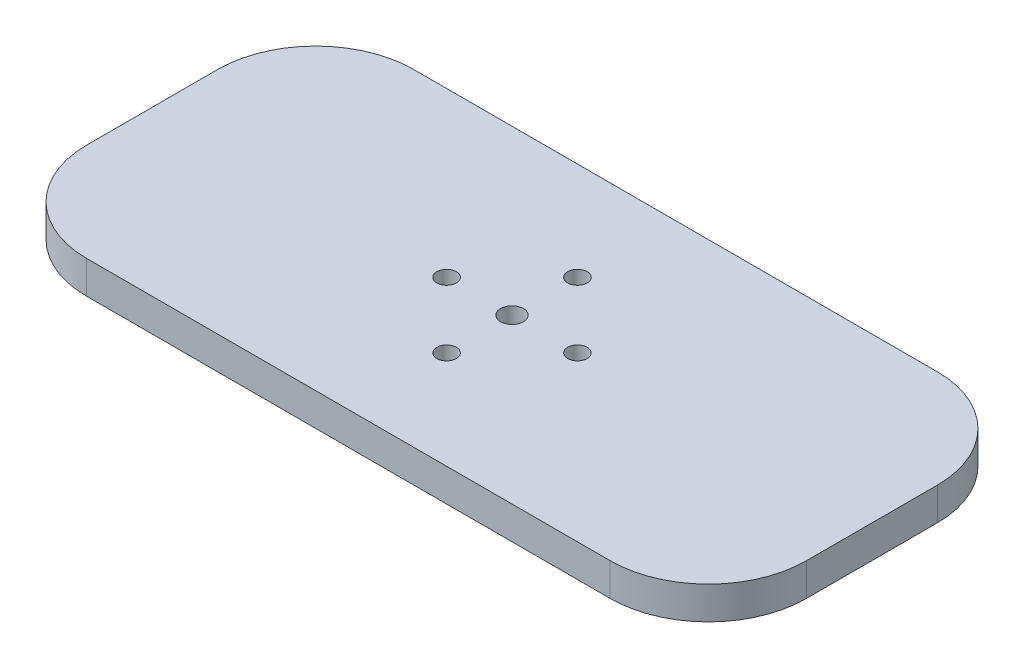
SolidWorks part; units mm, degrees
ref_plane "Front Plane" through (0, 0, 0) normal (0, 0, 1) x (1, 0, 0)
ref_plane "Top Plane" through (0, 0, 0) normal (0, 1, 0) x (1, 0, 0)
ref_plane "Right Plane" through (0, 0, 0) normal (1, 0, 0) x (0, 0, -1)
sketch "Sketch1" plane through (0, 0, 0) normal (0, 1, 0) x (1, 0, 0)
  line L1 (-69.85, -31.75) -> (69.85, -31.75)
  line L2 (-69.85, -31.75) -> (-69.85, 31.75)
  line L3 (-69.85, 31.75) -> (69.85, 31.75)
  line L4 (69.85, -31.75) -> (69.85, 31.75)
  line L5 (-69.85, -31.75) -> (69.85, 31.75) construction
  line L6 (-69.85, 31.75) -> (69.85, -31.75) construction
  point P0 (0, 0)
  dimension "D1" = 139.7
  dimension "D2" = 63.5
extrude "Boss-Extrude1" add sketch "Sketch1" along normal mid plane 6.35
sketch "Sketch2" plane through (0, 3.175, 0) normal (0, 1, 0) x (1, 0, 0)
  line L0 (0, -12.7) -> (0, 12.7) construction
  line L1 (-12.7, 0) -> (12.7, 0) construction
  point P4 (0, 0)
  point P8 (0, 0)
  dimension "D1" = 25.4
hole_wizard "#6 Clearance Hole1" positions "Sketch3" profile "Sketch4" hole size "#6" standard "ANSI Inch" end condition up to next
sketch "Sketch3" plane through (0, 3.175, 0) normal (0, 1, 0) x (1, 0, 0)
  point P0 (0, 12.7)
  point P3 (-12.7, 0)
  point P6 (0, -12.7)
  point P9 (12.7, 0)
sketch "Sketch4" plane through (0, 3.175, -12.7) normal (1, 0, 0) x (0, 0, 1)
  line L0 (0, 0) -> (0, 6.35)
  line L1 (0, 6.35) -> (1.8986, 6.35)
  line L2 (1.8986, 6.35) -> (1.8986, 0)
  line L5 (1.8986, 0) -> (0, 0)
  line L11 (0, -6.35) -> (0, 107.95) construction
  dimension "Thru Hole Dia." = 3.7973
  dimension "Thru Hole Depth" = 6.35
fillet "Fillet1" radius 19.05 4 edges at (69.85, 0, -31.75) (69.85, 0, 31.75) (-69.85, 0, 31.75) (-69.85, 0, -31.75)
sketch "Sketch5" plane through (0, 3.175, 0) normal (0, 1, 0) x (1, 0, 0)
  circle A0 centre (0, 0) radius 2.2225
  dimension "D1" = 4.445
extrude "Cut-Extrude1" cut sketch "Sketch5" against normal blind 6.35
